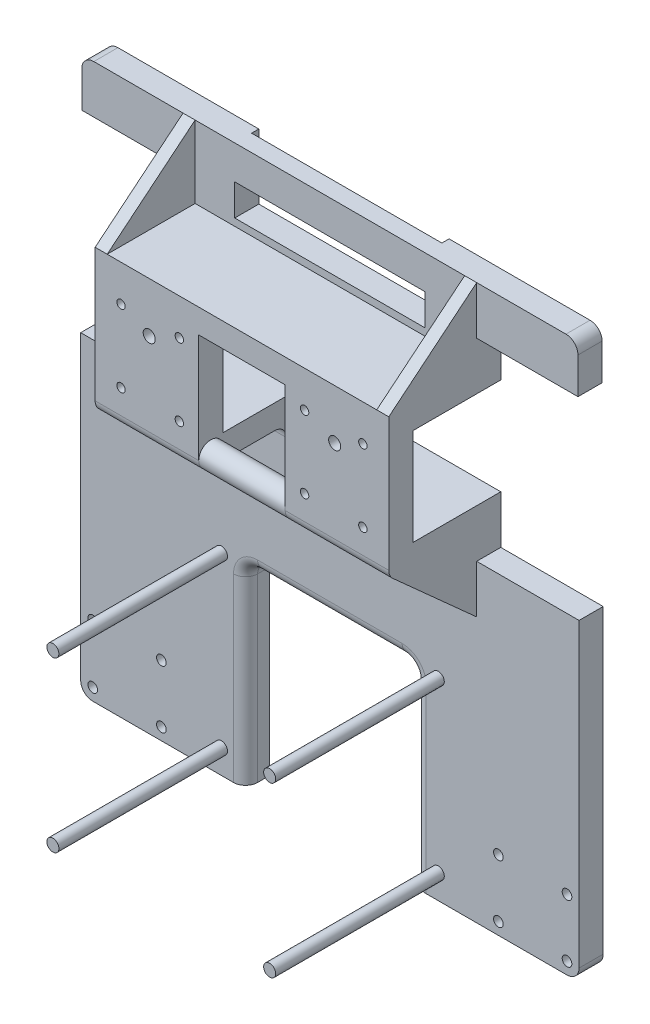
SolidWorks part; units mm, degrees
ref_plane "前视基准面" through (0, 0, 0) normal (0, 0, 1) x (1, 0, 0)
ref_plane "上视基准面" through (0, 0, 0) normal (0, 1, 0) x (1, 0, 0)
ref_plane "右视基准面" through (0, 0, 0) normal (1, 0, 0) x (0, 0, -1)
sketch "草图1" plane through (0, 0, 0) normal (0, 0, 1) x (1, 0, 0)
  line L0 (0.6204, 0) -> (-12.9506, 0) construction
  line L1 (0, 0.3624) -> (0, -16.9474) construction
  line L2 (-26, -85) -> (26, -85) construction
  line L3 (-62.248, -100) -> (42.4192, -100) construction
  line L4 (-60.95, -120.1) -> (-17.95, -120.1)
  line L5 (-60.95, -79.9) -> (-17.95, -79.9)
  line L6 (-60.95, -79.9) -> (-60.95, -120.1)
  line L7 (60.95, -120.1) -> (17.95, -120.1)
  line L8 (60.95, -79.9) -> (17.95, -79.9)
  line L9 (60.95, -79.9) -> (60.95, -120.1)
  line L10 (-17.95, -79.9) -> (-17.95, -120.1)
  line L11 (17.95, -79.9) -> (17.95, -120.1)
  circle A0 centre (-26, -85) radius 1.75
  circle A1 centre (26, -85) radius 1.75
  circle A2 centre (-50.2, -85) radius 1.75
  circle A3 centre (50.2, -85) radius 1.75
  circle A4 centre (50.2, -115) radius 1.75
  circle A5 centre (26, -115) radius 1.75
  circle A6 centre (-26, -115) radius 1.75
  circle A7 centre (-50.2, -115) radius 1.75
  dimension "D2" = 3.5
  dimension "D3" = 3.5
  dimension "D1" = 52
  dimension "D4" = 24.2
  dimension "D5" = 15
  dimension "D6" = 43
  dimension "D7" = 40.2
  dimension "D8" = 10.75
  dimension "D9" = 100
sketch "草图2" plane through (0, 0, 0) normal (0, 0, 1) x (1, 0, 0)
  line L4 (-60.95, -120.1) -> (-17.95, -120.1)
  line L5 (-17.95, -120.1) -> (-17.95, -79.9)
  line L6 (-17.95, -79.9) -> (-60.95, -79.9)
  line L7 (-60.95, -79.9) -> (-60.95, -120.1)
  line L8 (-60.95, -120.1) -> (-17.95, -120.1)
  line L9 (-17.95, -120.1) -> (-17.95, -79.9)
  line L10 (-17.95, -79.9) -> (-60.95, -79.9)
  line L11 (-60.95, -79.9) -> (-60.95, -120.1)
  line L12 (17.95, -79.9) -> (17.95, -120.1)
  line L13 (17.95, -120.1) -> (60.95, -120.1)
  line L14 (60.95, -120.1) -> (60.95, -79.9)
  line L15 (60.95, -79.9) -> (17.95, -79.9)
  line L16 (17.95, -79.9) -> (17.95, -120.1)
  line L17 (17.95, -120.1) -> (60.95, -120.1)
  line L18 (60.95, -120.1) -> (60.95, -79.9)
  line L19 (60.95, -79.9) -> (17.95, -79.9)
  circle A1 centre (50.2, -85) radius 1.75
  circle A2 centre (50.2, -85) radius 1.75
  circle A3 centre (-50.2, -85) radius 1.75
  circle A4 centre (-50.2, -85) radius 1.75
  circle A5 centre (26, -85) radius 1.75
  circle A6 centre (26, -85) radius 1.75
  circle A7 centre (-26, -85) radius 1.75
  circle A8 centre (-26, -85) radius 1.75
  circle A9 centre (-50.2, -115) radius 1.75
  circle A10 centre (-50.2, -115) radius 1.75
  circle A11 centre (-26, -115) radius 1.75
  circle A12 centre (-26, -115) radius 1.75
  circle A13 centre (26, -115) radius 1.75
  circle A14 centre (26, -115) radius 1.75
  circle A15 centre (50.2, -115) radius 1.75
  circle A16 centre (50.2, -115) radius 1.75
  dimension "D1" = 0
  dimension "D2" = 0
  dimension "D3" = 0
  dimension "D4" = 0
  dimension "D5" = 0
  dimension "D6" = 0
  dimension "D7" = 0
  dimension "D8" = 0
  dimension "D9" = 0
  dimension "D10" = 0
extrude "凸台-拉伸1" add sketch "草图2" along normal blind 10
sketch "草图3" plane through (0, -120.1, 0) normal (0, -1, 0) x (1, 0, 0)
  line L0 (17.95, 10) -> (17.95, 0) construction
  line L1 (60.95, 10) -> (17.95, 10)
  line L2 (60.95, 10) -> (60.95, -26.5)
  line L3 (60.95, -26.5) -> (17.95, -26.5)
  line L4 (17.95, 10) -> (17.95, -26.5)
  line L5 (-60.95, 10) -> (-60.95, 0) construction
  line L6 (-17.95, 10) -> (-60.95, 10)
  line L7 (-17.95, 10) -> (-17.95, -26.5)
  line L8 (-17.95, -26.5) -> (-60.95, -26.5)
  line L9 (-60.95, 10) -> (-60.95, -26.5)
  dimension "D1" = 36.5
  dimension "D2" = 36.5
extrude "凸台-拉伸2" add sketch "草图3" along normal blind 10
sketch "草图4" plane through (0, 0, -26.5) normal (0, 0, -1) x (-1, 0, 0)
  line L0 (60.95, -130.1) -> (60.95, -120.1) construction
  line L1 (-60.95, -120.1) -> (60.95, -120.1)
  line L2 (-60.95, -120.1) -> (-60.95, -270.1)
  line L3 (-60.95, -270.1) -> (60.95, -270.1)
  line L4 (60.95, -120.1) -> (60.95, -270.1)
  dimension "D1" = 150
extrude "凸台-拉伸3" add sketch "草图4" along normal blind 10
sketch "草图6" plane through (0, -79.9, 0) normal (0, 1, 0) x (1, 0, 0)
  line L0 (60.95, -10) -> (60.95, 0) construction
  line L1 (-60.95, -10) -> (60.95, -10)
  line L2 (-60.95, -10) -> (-60.95, 26.5)
  line L3 (-60.95, 26.5) -> (60.95, 26.5)
  line L4 (60.95, -10) -> (60.95, 26.5)
  dimension "D1" = 36.5
extrude "凸台-拉伸4" add sketch "草图6" along normal blind 10
sketch "草图7" plane through (17.95, 0, 0) normal (-1, 0, 0) x (0, 0, 1)
  line L0 (10, -130.1) -> (-26.5, -130.1) construction
  line L1 (10, -79.9) -> (10, -130.1) construction
  circle A0 centre (5, -125.1) radius 5
  dimension "D1" = 10
extrude "凸台-拉伸5" add sketch "草图7" along normal up to next
fillet "圆角1" radius 5 2 edges at (-39.45, -130.1, 10) (39.45, -130.1, 10)
fillet "圆角2" radius 5 2 edges at (-39.45, -130.1, -26.5) (39.45, -130.1, -26.5)
sketch "草图8" plane through (0, 0, -26.5) normal (0, 0, -1) x (-1, 0, 0)
  line L0 (-60.95, -79.9) -> (60.95, -79.9) construction
  line L1 (-60.95, -79.9) -> (60.95, -79.9)
  line L2 (-103, -59.9) -> (-103, -39.9)
  line L3 (-103, -39.9) -> (103, -39.9)
  line L4 (103, -59.9) -> (103, -39.9)
  line L5 (0, -69.9) -> (0, -79.9) construction
  line L6 (-60.95, -69.9) -> (60.95, -69.9) construction
  line L9 (60.95, -79.9) -> (60.95, -59.9)
  line L10 (60.95, -59.9) -> (103, -59.9)
  line L13 (-60.95, -79.9) -> (-60.95, -59.9)
  line L14 (-60.95, -59.9) -> (-103, -59.9)
  dimension "D1" = 20
  dimension "D2" = 206
  dimension "D3" = 20
  dimension "D4" = 20
extrude "凸台-拉伸6" add sketch "草图8" along normal blind 10
sketch "草图9" plane through (0, 0, -36.5) normal (0, 0, -1) x (-1, 0, 0)
  line L0 (0, -39.9) -> (0, -79.9) construction
  line L1 (103, -39.9) -> (-103, -39.9) construction
  line L2 (-60.95, -79.9) -> (60.95, -79.9) construction
  line L4 (-39.5, -39.9) -> (39.5, -39.9)
  line L5 (-39.5, -39.9) -> (-39.5, -66.9)
  line L6 (-39.5, -66.9) -> (39.5, -66.9)
  line L7 (39.5, -39.9) -> (39.5, -66.9)
  dimension "D1" = 79
  dimension "D2" = 27
extrude "切除-拉伸1" cut sketch "草图9" against normal blind 3
sketch "草图10" plane through (0, 0, -33.5) normal (0, 0, -1) x (-1, 0, 0)
  line L0 (39.5, -66.9) -> (39.5, -39.9) construction
  line L1 (-39.5, -66.9) -> (39.5, -66.9)
  line L2 (-39.5, -66.9) -> (-39.5, -53.9)
  line L3 (-39.5, -53.9) -> (39.5, -53.9)
  line L4 (39.5, -66.9) -> (39.5, -53.9)
  dimension "D1" = 13
extrude "切除-拉伸2" cut sketch "草图10" against normal through all
sketch "草图11" plane through (-60.95, 0, 0) normal (-1, 0, 0) x (0, 0, 1)
  line L0 (10, -69.9) -> (-26.5, -39.9)
  line L1 (-26.5, -69.9) -> (-26.5, -59.9) construction
  dimension "D1" = 30
rib "筋16" sketch "草图11" sketch "草图11" thickness 5 extrusion direction parallel to sketch draft on no parameters "D1"=5
mirror "镜向1" about plane through (0, 0, 0) normal (1, 0, 0) of "筋16"
sketch "草图12" plane through (-60.95, 0, 0) normal (-1, 0, 0) x (0, 0, 1)
  line L0 (-26.5, -270.1) -> (-26.5, -135.1) construction
  line L1 (-26.5, -140.1) -> (-36.5, -140.1)
  line L2 (-26.5, -140.1) -> (-26.5, -270.1)
  line L3 (-26.5, -270.1) -> (-36.5, -270.1)
  line L4 (-36.5, -140.1) -> (-36.5, -270.1)
  line L5 (0, -120.1) -> (-36.5, -120.1) construction
  dimension "D1" = 20
extrude "凸台-拉伸7" add sketch "草图12" along normal blind 42.5
mirror "镜向2" about plane through (0, 0, 0) normal (1, 0, 0) of "凸台-拉伸7"
sketch "草图13" plane through (0, 0, -26.5) normal (0, 0, 1) x (1, 0, 0)
  line L0 (98.45, -265.1) -> (98.45, -241.1) construction
  line L1 (98.45, -265.1) -> (69.95, -265.1) construction
  line L2 (69.95, -241.1) -> (69.95, -265.1) construction
  line L3 (69.95, -241.1) -> (98.45, -241.1) construction
  line L4 (103.45, -270.1) -> (103.45, -140.1) construction
  line L5 (103.45, -270.1) -> (-103.45, -270.1) construction
  circle A0 centre (98.45, -265.1) radius 2
  circle A1 centre (98.45, -241.1) radius 2
  circle A2 centre (69.95, -265.1) radius 2
  circle A3 centre (69.95, -241.1) radius 2
  dimension "D1" = 4
  dimension "D2" = 4
  dimension "D5" = 4
  dimension "D6" = 4
  dimension "D3" = 24
  dimension "D4" = 28.5
  dimension "D7" = 5
  dimension "D8" = 5
extrude "切除-拉伸3" cut sketch "草图13" against normal blind 42.5
mirror "镜向3" about plane through (0, 0, 0) normal (1, 0, 0) of "切除-拉伸3"
sketch "草图14" plane through (0, 0, -26.5) normal (0, 0, 1) x (1, 0, 0)
  line L0 (0, -120.1) -> (0, -270.1) construction
  line L1 (-17.95, -120.1) -> (17.95, -120.1) construction
  line L2 (103.45, -270.1) -> (-103.45, -270.1) construction
  line L3 (103.45, -270.1) -> (-103.45, -270.1) construction
  circle A0 centre (-45, -260.1) radius 2.5
  circle A1 centre (45, -260.1) radius 2.5
  circle A2 centre (-45, -190.1) radius 2.5
  circle A3 centre (45, -190.1) radius 2.5
  dimension "D1" = 5
  dimension "D3" = 5
  dimension "D2" = 90
  dimension "D4" = 90
  dimension "D5" = 70
  dimension "D6" = 10
extrude "凸台-拉伸8" add sketch "草图14" along normal blind 70
sketch "草图15" plane through (0, 0, -26.5) normal (0, 0, 1) x (1, 0, 0)
  line L0 (103.45, -270.1) -> (-103.45, -270.1) construction
  line L1 (-35, -270.1) -> (35, -270.1)
  line L2 (-35, -270.1) -> (-35, -190.1)
  line L3 (-35, -190.1) -> (35, -190.1)
  line L4 (35, -270.1) -> (35, -190.1)
  line L7 (0, -120.1) -> (0, -270.1) construction
  line L8 (-17.95, -120.1) -> (17.95, -120.1) construction
  dimension "D1" = 70
  dimension "D2" = 80
extrude "切除-拉伸4" cut sketch "草图15" against normal blind 60
sketch "草图16" plane through (-60.95, 0, 0) normal (-1, 0, 0) x (0, 0, 1)
  line L0 (8.3403, -128.8205) -> (-26.5, -160.1)
  line L1 (-26.5, -140.1) -> (-26.5, -160.1) construction
  arc A0 (5, -130.1) -> (10, -125.1) centre (5, -125.1) ccw construction
  dimension "D1" = 20
rib "筋17" sketch "草图16" sketch "草图16" thickness 5 extrusion direction parallel to sketch draft on no parameters "D1"=5
mirror "镜向4" about plane through (0, 0, 0) normal (1, 0, 0) of "筋17"
fillet "圆角4" radius 5 2 edges at (103, -39.9, -31.5) (-103, -39.9, -31.5)
fillet "圆角5" radius 5 2 edges at (103.45, -270.1, -31.5) (-103.45, -270.1, -31.5)
fillet "圆角6" radius 5 5 edges at (-35, -190.1, -31.5) (35, -190.1, -31.5) (-35, -230.1, -26.5) (0, -190.1, -26.5) (35, -230.1, -26.5)
sketch "草图17" plane through (0, 0, 10) normal (0, 0, 1) x (1, 0, 0)
  line L0 (-55.95, -69.9) -> (55.95, -69.9) construction
  line L1 (60.95, -125.1) -> (60.95, -69.9) construction
  line L2 (0, -44) -> (0, 44) construction
  circle A0 centre (38.5, -90.6) radius 2.5
  circle A1 centre (-38.5, -90.6) radius 2.5
  dimension "D1" = 5
  dimension "D2" = 20.7
  dimension "D3" = 22.45
extrude "切除-拉伸5" cut sketch "草图17" against normal through all
